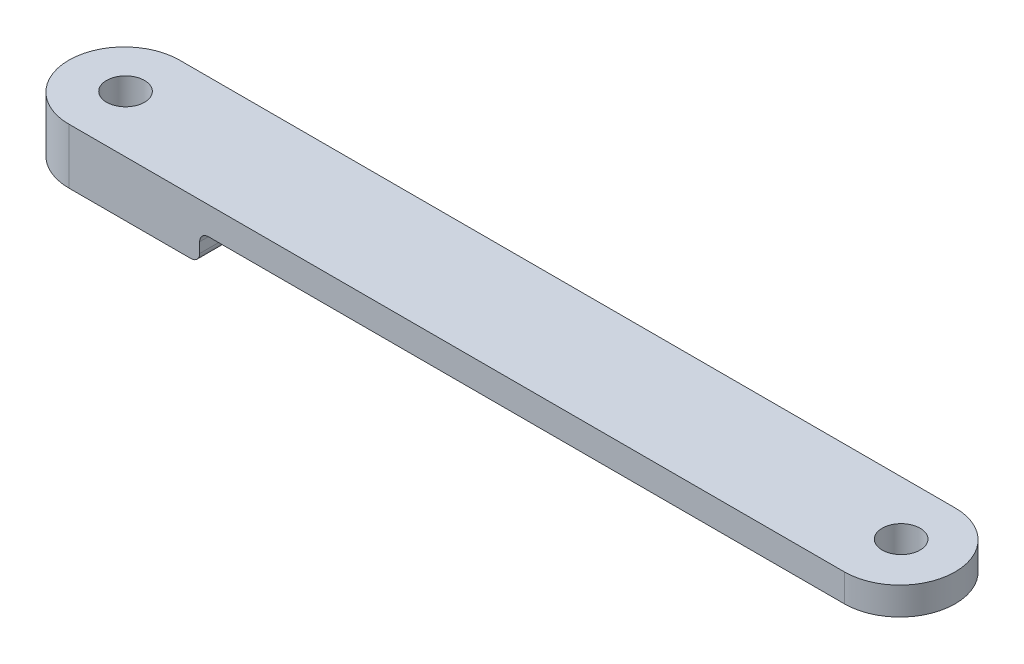
SolidWorks part; units mm, degrees
material "PET"
ref_plane "Front" through (0, 0, 0) normal (0, 0, 1) x (1, 0, 0)
ref_plane "Top" through (0, 0, 0) normal (0, 1, 0) x (1, 0, 0)
ref_plane "Right" through (0, 0, 0) normal (1, 0, 0) x (0, 0, -1)
sketch "Sketch1" plane through (0, 0, 0) normal (0, 1, 0) x (1, 0, 0)
  line L1 (-23.1719, 5.6259) -> (65.7281, 5.6259)
  line L3 (-23.1719, -7.0741) -> (65.7281, -7.0741)
  line L5 (-23.1719, 5.6259) -> (65.7281, -7.0741) construction
  line L6 (-23.1719, -7.0741) -> (65.7281, 5.6259) construction
  arc A0 (-23.1719, 5.6259) -> (-23.1719, -7.0741) centre (-23.1719, -0.7241) ccw
  arc A1 (65.7281, 5.6259) -> (65.7281, -7.0741) centre (65.7281, -0.7241) cw
  point P4 (21.2781, -0.7241)
  dimension "D1" = 6.35
  dimension "D2" = 88.9
extrude "Boss-Extrude1" add sketch "Sketch1" along normal blind 3.175
sketch "Sketch2" plane through (0, 3.175, 0) normal (0, 1, 0) x (1, 0, 0)
  line L0 (-23.1719, -0.5708) -> (40.067, -0.5708) construction
  circle A0 centre (-23.1719, -0.5708) radius 2.175
  circle A2 centre (65.7281, -0.5708) radius 2.175
  dimension "D1" = 4.35
  dimension "D2" = 88.9
  dimension "D3" = 4.35
extrude "Cut-Extrude1" cut sketch "Sketch2" against normal blind 12.7
sketch "Sketch4" plane through (0, 0, 0) normal (0, -1, 0) x (1, 0, 0)
  line L0 (-23.1719, 7.0741) -> (-8.1719, 7.0741)
  line L1 (-23.1719, 7.0741) -> (65.7281, 7.0741) construction
  line L2 (-8.1719, 7.0741) -> (-8.1719, -5.6259)
  line L3 (65.7281, -5.6259) -> (-23.1719, -5.6259) construction
  line L4 (-8.1719, -5.6259) -> (-23.1719, -5.6259)
  arc A0 (-23.1719, 7.0741) -> (-23.1719, -5.6259) centre (-23.1719, 0.7241) ccw
  arc A2 (-23.1719, 7.0741) -> (-23.1719, -5.6259) centre (-23.1719, 0.7241) ccw construction
  circle A3 centre (-23.1719, 0.5708) radius 2.175
  dimension "D1" = 12.7
  dimension "D2" = 15
extrude "Boss-Extrude3" add sketch "Sketch4" along normal blind 3.175
fillet "Fillet1" radius 1 2 edges at (-8.1719, -3.175, 0.7241) (-8.1719, 0, 0.7241)
